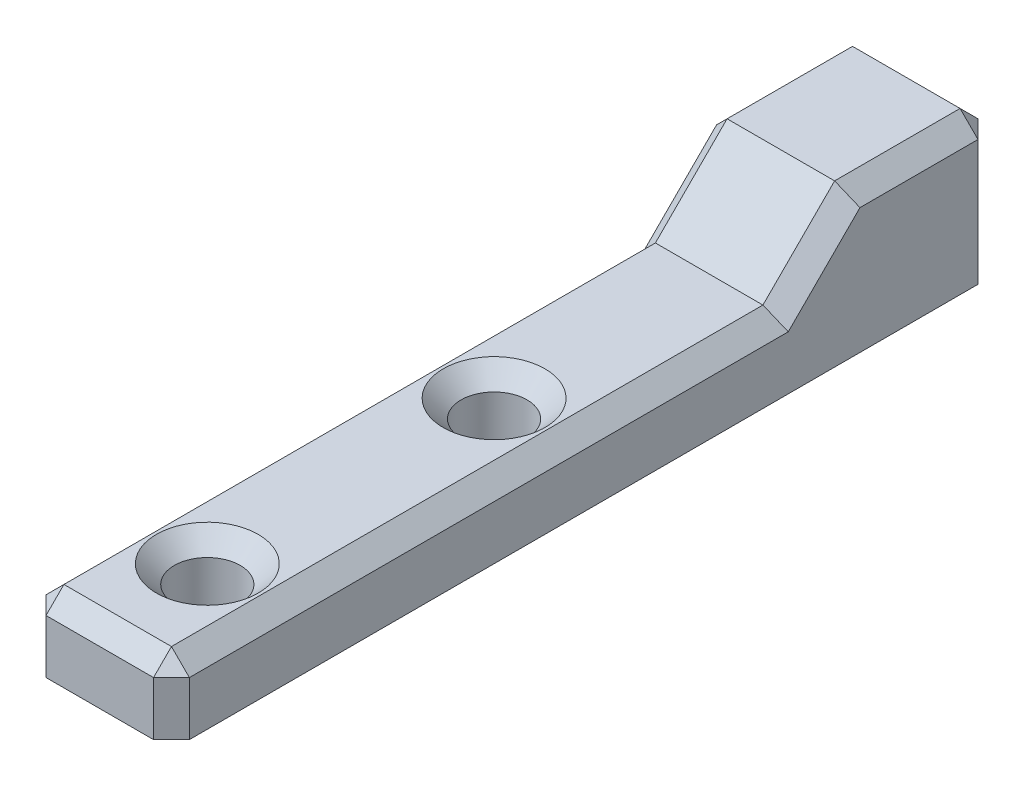
SolidWorks part; units mm, degrees
ref_plane "Front Plane" through (0, 0, 0) normal (0, 0, 1) x (1, 0, 0)
ref_plane "Top Plane" through (0, 0, 0) normal (0, 1, 0) x (1, 0, 0)
ref_plane "Right Plane" through (0, 0, 0) normal (1, 0, 0) x (0, 0, -1)
sketch "Sketch1" plane through (0, 0, 0) normal (0, 1, 0) x (1, 0, 0)
  line L1 (0, 0) -> (12.7, 0)
  line L2 (0, 0) -> (0, 73.025)
  line L3 (0, 73.025) -> (12.7, 73.025)
  line L4 (12.7, 0) -> (12.7, 73.025)
  circle A0 centre (6.35, 9.525) radius 2.921
  circle A1 centre (6.35, 34.925) radius 2.921
  dimension "D3" = 5.842
  dimension "D1" = 12.7
  dimension "0.375" = 9.525
  dimension "D4" = 25.4
  dimension "D5" = 38.1
extrude "Boss-Extrude1" add sketch "Sketch1" along normal blind 12.7
sketch "Sketch2" plane through (12.7, 0, 0) normal (1, 0, 0) x (0, 0, -1)
  line L0 (73.025, 12.7) -> (73.025, 0) construction
  line L1 (0, 12.7) -> (60.325, 12.7)
  line L2 (0, 12.7) -> (0, 6.35)
  line L3 (0, 6.35) -> (60.325, 6.35)
  line L4 (60.325, 12.7) -> (60.325, 6.35)
  dimension "D1" = 12.7
  dimension "D2" = 6.35
extrude "Cut-Extrude1" cut sketch "Sketch2" against normal through all
chamfer "Chamfer1" distance 6.35 angle 45 1 edges at (6.35, 6.35, -60.325)
chamfer "Chamfer2" distance 1.5875 angle 45 14 edges at (0, 3.175, 0) (12.7, 3.175, 0) (0, 6.35, -73.025) (12.7, 6.35, -73.025) (0, 9.525, -57.15) (0, 12.7, -66.675) (6.35, 12.7, -73.025) (12.7, 12.7, -66.675) (12.7, 9.525, -57.15) (0, 6.35, -26.9875) (6.35, 6.35, 0) (12.7, 6.35, -26.9875) (6.35, 6.35, -12.446) (6.35, 6.35, -37.846)
